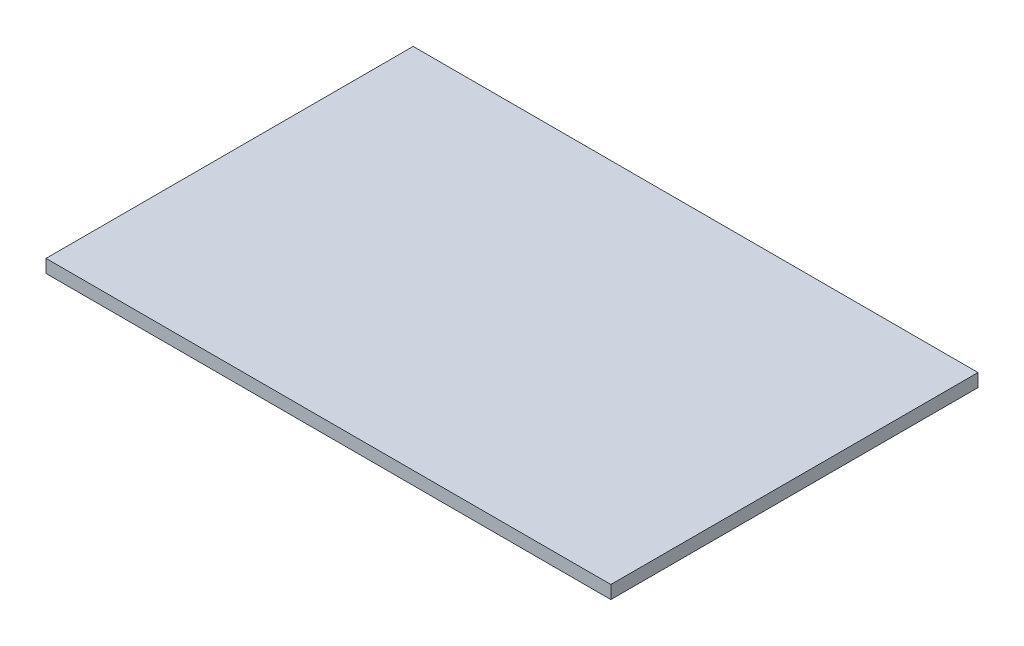
SolidWorks part; units mm, degrees
material "Copper"
ref_plane "Front Plane" through (0, 0, 0) normal (0, 0, 1) x (1, 0, 0)
ref_plane "Top Plane" through (0, 0, 0) normal (0, 1, 0) x (1, 0, 0)
ref_plane "Right Plane" through (0, 0, 0) normal (1, 0, 0) x (0, 0, -1)
sketch "Sketch1" plane through (0, 0, 0) normal (0, 1, 0) x (1, 0, 0)
  line L1 (0, 0) -> (31.75, 0)
  line L2 (0, 0) -> (0, 20.6375)
  line L3 (0, 20.6375) -> (31.75, 20.6375)
  line L4 (31.75, 0) -> (31.75, 20.6375)
  dimension "D1" = 20.6375
  dimension "D2" = 31.75
base flange "Base-Flange1" sketch "Sketch1" thickness 0.7366 reverse thickness direction no parameters "D1"=0.7366
sketch "Sketch6" plane through (0, 0, 0) normal (0, 1, 0) x (1, 0, 0)
  line L0 (15.875, 20.6375) -> (15.875, 0)
  line L1 (0, 20.6375) -> (31.75, 20.6375) construction
  line L2 (0, 0) -> (31.75, 0) construction
  line L3 (0, 10.3187) -> (31.75, 10.3187)
  line L4 (0, 20.6375) -> (0, 0) construction
  line L5 (31.75, 0) -> (31.75, 20.6375) construction
  line L6 (31.75, 20.6375) -> (28.461, 20.6375)
  line L7 (31.75, 20.6375) -> (0, 20.6375) construction
  line L8 (28.461, 20.6375) -> (28.461, 17.5829)
  line L9 (28.461, 17.5829) -> (31.75, 17.5829)
  line L10 (31.75, 17.5829) -> (31.75, 20.6375)
  dimension "D1" = 3.289
sketch "Bend-Lines1" [suppressed] plane through (0, 0, 0) normal (0, 1, 0) x (1, 0, 0)
sketch "Bounding-Box1" [suppressed] plane through (0, 0, 0) normal (0, 1, 0) x (1, 0, 0)
sheet metal parameters "Sheet-Metal1" thickness 0.7366 parameters "D1"=0.7366
flat pattern "Flat-Pattern1" [suppressed]
sketch "Bend-Lines2" plane through (0, 0, 0) normal (0, 1, 0) x (1, 0, 0)
sketch3d "Bounding-Box2" [suppressed]
  line L0 (-31.75, 20.6375, 0) -> (0, 20.6375, 0) construction
  line L1 (-31.75, 0, 0) -> (0, 0, 0) construction
  line L2 (-31.75, 20.6375, 0) -> (-31.75, 0, 0) construction
  line L3 (0, 20.6375, 0) -> (0, 0, 0) construction
